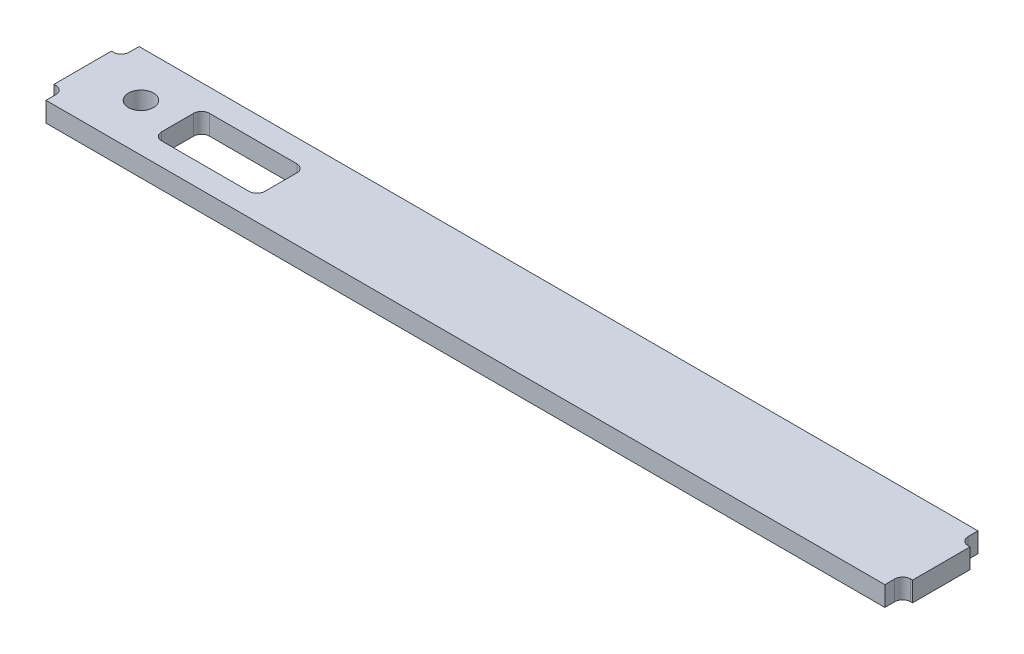
SolidWorks part; units mm, degrees
ref_plane "Front Plane" through (0, 0, 0) normal (0, 0, 1) x (1, 0, 0)
ref_plane "Top Plane" through (0, 0, 0) normal (0, 1, 0) x (1, 0, 0)
ref_plane "Right Plane" through (0, 0, 0) normal (1, 0, 0) x (0, 0, -1)
sketch "Sketch1" plane through (0, 0, 0) normal (0, 1, 0) x (1, 0, 0)
  line L1 (336.55, 37.3714) -> (-336.55, 37.3714)
  line L2 (336.55, 37.3714) -> (336.55, -37.3714)
  line L3 (336.55, -37.3714) -> (-336.55, -37.3714)
  line L4 (-336.55, 37.3714) -> (-336.55, -37.3714)
  line L5 (336.55, 37.3714) -> (-336.55, -37.3714) construction
  line L6 (336.55, -37.3714) -> (-336.55, 37.3714) construction
  point P0 (0, 0)
  dimension "D1" = 673.1
  dimension "D2" = 74.7428
extrude "Boss-Extrude1" add sketch "Sketch1" along normal blind 15.875
sketch "Sketch2" plane through (0, 15.875, 0) normal (0, 1, 0) x (1, 0, 0)
  line L0 (336.55, 37.3714) -> (-336.55, 37.3714) construction
  line L1 (344.4875, 18.3214) -> (-344.4875, 18.3214)
  line L2 (344.4875, 18.3214) -> (344.4875, -18.3214)
  line L3 (344.4875, -18.3214) -> (-344.4875, -18.3214)
  line L4 (-344.4875, 18.3214) -> (-344.4875, -18.3214)
  line L5 (344.4875, 18.3214) -> (-344.4875, -18.3214) construction
  line L6 (344.4875, -18.3214) -> (-344.4875, 18.3214) construction
  line L7 (-336.55, 37.3714) -> (-336.55, -37.3714) construction
  point P0 (0, 0)
  dimension "D1" = 19.05
  dimension "D2" = 7.9375
extrude "Boss-Extrude2" [suppressed] add sketch "Sketch2" against normal up to surface (15.875 mm away) up to face at (0, 0, 0)
fillet "Fillet1" [suppressed] radius 6.35
sketch "Sketch3" plane through (0, 15.875, 0) normal (0, 1, 0) x (1, 0, 0)
  line L0 (-336.55, -37.3714) -> (336.55, -37.3714) construction
  line L2 (-336.55, 37.3714) -> (-336.55, -37.3714) construction
  circle A0 centre (-298.45, 0.7286) radius 10.1
  dimension "D3" = 20.2
  dimension "D1" = 38.1
  dimension "D2" = 38.1
extrude "Cut-Extrude1" cut sketch "Sketch3" against normal through all both and the other way through all
sketch "Sketch4" plane through (0, 15.875, 0) normal (0, 1, 0) x (1, 0, 0)
  line L0 (-336.55, 37.3714) -> (-336.55, -37.3714) construction
  line L1 (-336.55, 23.0839) -> (-344.4875, 23.0839)
  line L2 (-336.55, 23.0839) -> (-336.55, -23.0839)
  line L3 (-336.55, -23.0839) -> (-344.4875, -23.0839)
  line L4 (-344.4875, 23.0839) -> (-344.4875, -23.0839)
  line L5 (336.55, 37.3714) -> (-336.55, 37.3714) construction
  line L6 (-336.55, -37.3714) -> (336.55, -37.3714) construction
  line L7 (0, -5.1837) -> (0, 37.3714) construction
  line L8 (344.4875, 23.0839) -> (344.4875, -23.0839)
  line L9 (336.55, -23.0839) -> (344.4875, -23.0839)
  line L10 (336.55, 23.0839) -> (336.55, -23.0839)
  line L11 (336.55, 23.0839) -> (344.4875, 23.0839)
  dimension "D1" = 14.2875
  dimension "D2" = 14.2875
  dimension "D3" = 7.9375
  dimension "D4" = 688.975
extrude "Boss-Extrude3" add sketch "Sketch4" against normal up to surface (15.875 mm away) up to face at (-298.45, 0, 9.3714)
fillet "Fillet2" radius 6.35 4 edges at (336.55, 7.9375, 23.0839) (336.55, 7.9375, -23.0839) (-336.55, 7.9375, 23.0839) (-336.55, 7.9375, -23.0839)
sketch "Sketch5" plane through (0, 15.875, 0) normal (0, 1, 0) x (1, 0, 0)
  line L0 (0, 0) -> (-185.4835, 0) construction
  line L1 (-268.2875, -19.177) -> (-185.4835, -19.177)
  line L2 (-268.2875, -19.177) -> (-268.2875, 19.177)
  line L3 (-268.2875, 19.177) -> (-185.4835, 19.177)
  line L4 (-185.4835, -19.177) -> (-185.4835, 19.177)
  line L5 (-344.4875, 23.0839) -> (-344.4875, -23.0839) construction
  dimension "D1" = 82.804
  dimension "D2" = 38.354
  dimension "D3" = 76.2
extrude "Cut-Extrude2" cut sketch "Sketch5" against normal through all both and the other way through all
fillet "Fillet3" radius 6.35 4 edges at (-268.2875, 7.9375, -19.177) (-185.4835, 7.9375, -19.177) (-185.4835, 7.9375, 19.177) (-268.2875, 7.9375, 19.177)
